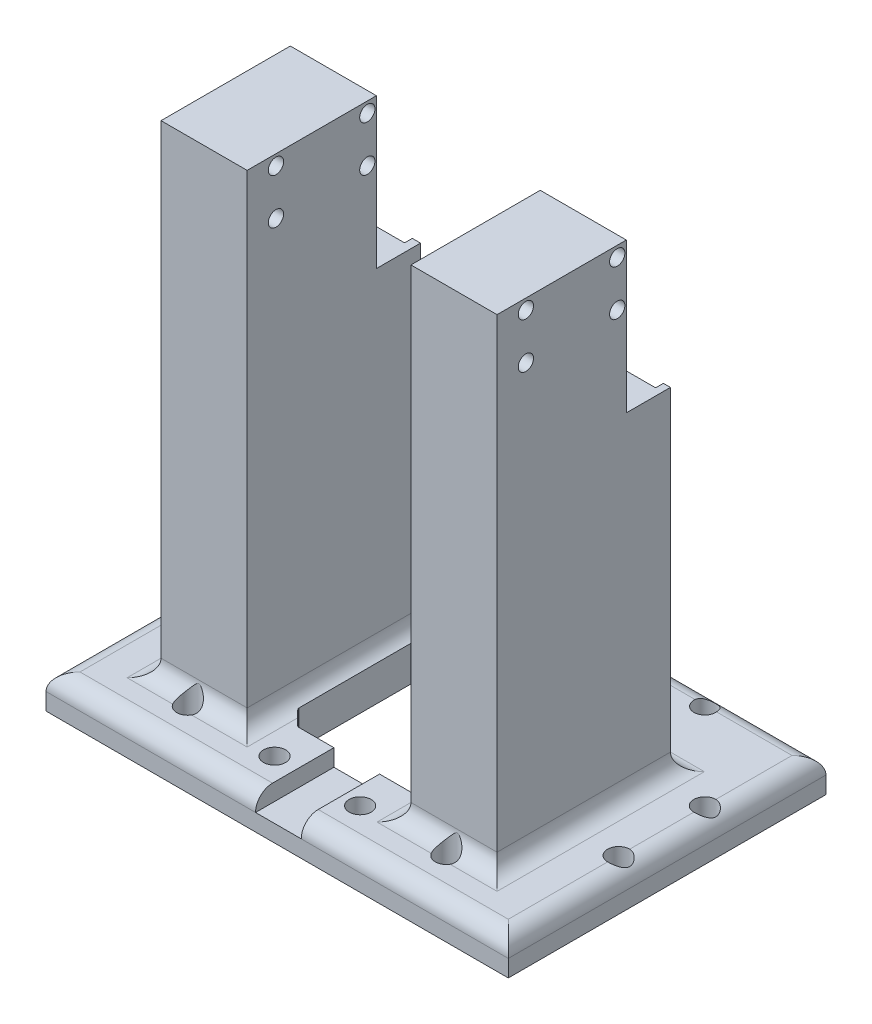
SolidWorks part; units mm, degrees
ref_plane "Front Plane" through (0, 0, 0) normal (0, 0, 1) x (1, 0, 0)
ref_plane "Top Plane" through (0, 0, 0) normal (0, 1, 0) x (1, 0, 0)
ref_plane "Right Plane" through (0, 0, 0) normal (1, 0, 0) x (0, 0, -1)
sketch "Sketch1" plane through (4645.495, -5615.4512, 222.287) normal (0, 1, 0) x (1, 0, 0)
  line L1 (-5.004, 249.919) -> (131.2605, 249.919)
  line L2 (-5.004, 249.919) -> (-5.004, 156.2902)
  line L4 (131.2605, 249.919) -> (131.2605, 156.2902)
  line L5 (-5.004, 156.2902) -> (63.1283, 156.2902)
  line L6 (63.1283, 156.2902) -> (131.2605, 156.2902)
extrude "Boss-Extrude1" add sketch "Sketch1" along normal blind 10
sketch "Sketch2" plane through (0, -5605.4512, 0) normal (0, 1, 0) x (1, 0, 0)
  line L0 (4708.449, 27.6321) -> (4708.449, -65.9968) construction
  line L1 (4658.9212, -50.5381) -> (4684.3037, -50.5381)
  line L2 (4658.9212, -50.5381) -> (4658.9212, 0.5715)
  line L3 (4658.9212, 0.5715) -> (4684.3037, 0.5715)
  line L4 (4684.3037, -50.5381) -> (4684.3037, 0.5715)
  line L6 (4640.4911, -65.9968) -> (4776.7555, -65.9968) construction
  line L7 (4732.5944, -50.5381) -> (4732.5944, 0.5715)
  line L8 (4757.9768, 0.5715) -> (4732.5944, 0.5715)
  line L9 (4757.9768, -50.5381) -> (4757.9768, 0.5715)
  line L10 (4757.9768, -50.5381) -> (4732.5944, -50.5381)
  line L11 (4640.4911, 27.6321) -> (4640.4911, -65.9968) construction
  dimension "D1" = 18.4301
  dimension "D2" = 43.8126
  dimension "D3" = 15.4587
  dimension "D4" = 66.5683
  dimension "D5" = 67.9579
extrude "Boss-Extrude2" add sketch "Sketch2" along normal blind 142.2321
sketch "Sketch3" plane through (0, 0, -0.5715) normal (0, 0, -1) x (-1, 0, 0)
  line L0 (-4737.0174, -5587.0652) -> (-4661.3426, -5587.0652) construction
  line L1 (-4661.3426, -5550.0756) -> (-4658.9212, -5550.0756) construction
  line L2 (-4661.3426, -5587.0652) -> (-4681.8823, -5587.0652)
  line L3 (-4661.3426, -5587.0652) -> (-4661.3426, -5463.2191)
  line L4 (-4661.3426, -5463.2191) -> (-4681.8823, -5463.2191)
  line L5 (-4681.8823, -5587.0652) -> (-4681.8823, -5463.2191)
  line L6 (-4658.9212, -5463.2191) -> (-4658.9212, -5605.4512) construction
  line L7 (-4681.8823, -5550.0756) -> (-4684.3037, -5550.0756) construction
  line L8 (-4684.3037, -5463.2191) -> (-4684.3037, -5605.4512) construction
  line L9 (-4684.3037, -5605.4512) -> (-4658.9212, -5605.4512) construction
  dimension "D1" = 2.4214
  dimension "D2" = 18.386
  dimension "D3" = 55.3755
  dimension "D4" = 142.2321
extrude "Cut-Extrude1" cut sketch "Sketch3" against normal blind 5.5
sketch "Sketch4" plane through (0, 0, 4.9285) normal (0, 0, -1) x (-1, 0, 0)
  line L0 (-4684.3037, -5463.2191) -> (-4684.3037, -5605.4512) construction
  line L1 (-4684.3037, -5507.3461) -> (-4658.9212, -5507.3461)
  line L2 (-4684.3037, -5507.3461) -> (-4684.3037, -5460.4819)
  line L3 (-4684.3037, -5460.4819) -> (-4658.9212, -5460.4819)
  line L4 (-4658.9212, -5507.3461) -> (-4658.9212, -5460.4819)
extrude "Cut-Extrude2" cut sketch "Sketch4" against normal blind 7.5 and the other way blind 12.5
fillet "Fillet14" radius 5 12 edges at (4745.2856, -5605.4512, -0.5715) (4732.5944, -5605.4512, 24.9833) (4745.2856, -5605.4512, 50.5381) (4757.9768, -5605.4512, 24.9833) (4684.3037, -5605.4512, 24.9833) (4671.6124, -5605.4512, -0.5715) (4658.9212, -5605.4512, 24.9833) (4671.6124, -5605.4512, 50.5381) (4708.6233, -5605.4512, -27.6321) (4776.7555, -5605.4512, 19.1824) (4708.6233, -5605.4512, 65.9968) (4640.4911, -5605.4512, 19.1824)
ref_plane "Plane1" through (4708.6233, 0, 0) normal (-1, 0, 0) x (0, 0, 1)
mirror "Mirror1" about plane through (4708.6233, 0, 0) normal (-1, 0, 0) of "Cut-Extrude1", "Cut-Extrude2"
sketch "Sketch5" plane through (0, 0, 4.9285) normal (0, 0, -1) x (-1, 0, 0)
  line L0 (-4661.3426, -5587.0652) -> (-4661.3426, -5507.3461) construction
  line L1 (-4661.3426, -5507.3461) -> (-4681.8823, -5507.3461) construction
  circle A0 centre (-4671.8428, -5574.7372) radius 1.6
  circle A1 centre (-4671.8428, -5528.736) radius 1.6
  circle A2 centre (-4745.0174, -5574.7372) radius 1.6
  circle A3 centre (-4745.0174, -5528.6285) radius 1.6
  dimension "D1" = 3.2
  dimension "D2" = 10.5002
  dimension "D3" = 83.6748
  dimension "D4" = 21.2824
  dimension "D5" = 21.3899
  dimension "D6" = 67.3911
extrude "Cut-Extrude3" cut sketch "Sketch5" against normal blind 5
sketch "Sketch6" plane through (0, -5615.4512, 0) normal (0, -1, 0) x (1, 0, 0)
  line L0 (4687.3481, 38.1501) -> (4687.3481, 5.4507)
  line L1 (4687.3481, 5.4507) -> (4687.3544, 5.3237)
  line L2 (4687.3544, 5.3237) -> (4687.3726, 5.2023)
  line L3 (4687.3726, 5.2023) -> (4687.4221, 5.0233)
  line L4 (4687.4221, 5.0233) -> (4687.4447, 4.9647)
  line L5 (4687.4447, 4.9647) -> (4687.5086, 4.8326)
  line L6 (4687.5086, 4.8326) -> (4687.5713, 4.7315)
  line L7 (4687.5713, 4.7315) -> (4687.6389, 4.6419)
  line L8 (4687.6389, 4.6419) -> (4687.72, 4.5526)
  line L9 (4687.72, 4.5526) -> (4687.845, 4.4277)
  line L10 (4687.845, 4.4277) -> (4691.1377, 1.135)
  line L11 (4691.1377, 1.135) -> (4691.2224, 1.0511)
  line L12 (4691.2224, 1.0511) -> (4691.2515, 1.0245)
  line L13 (4691.2515, 1.0245) -> (4691.2955, 0.9873)
  line L14 (4691.2955, 0.9873) -> (4691.3592, 0.9392)
  line L15 (4691.3592, 0.9392) -> (4691.4281, 0.8937)
  line L16 (4691.4281, 0.8937) -> (4691.5232, 0.8407)
  line L17 (4691.5232, 0.8407) -> (4691.6109, 0.7967)
  line L18 (4691.6109, 0.7967) -> (4691.844, 0.7303)
  line L19 (4691.844, 0.7303) -> (4691.8846, 0.7229)
  line L20 (4691.8846, 0.7229) -> (4692.0931, 0.7057)
  line L21 (4692.0931, 0.7057) -> (4724.7925, 0.7057)
  line L22 (4724.7925, 0.7057) -> (4724.9361, 0.7138)
  line L23 (4724.9361, 0.7138) -> (4725.0268, 0.7275)
  line L24 (4725.0268, 0.7275) -> (4725.101, 0.7437)
  line L25 (4725.101, 0.7437) -> (4725.1643, 0.7613)
  line L26 (4725.1643, 0.7613) -> (4725.2646, 0.7967)
  line L27 (4725.2646, 0.7967) -> (4725.3342, 0.827)
  line L28 (4725.3342, 0.827) -> (4725.3953, 0.8558)
  line L29 (4725.3953, 0.8558) -> (4725.4499, 0.8784)
  line L30 (4725.4499, 0.8784) -> (4725.4967, 0.9188)
  line L31 (4725.4967, 0.9188) -> (4725.5263, 0.9392)
  line L32 (4725.5263, 0.9392) -> (4729.1655, 4.5526)
  line L33 (4729.1655, 4.5526) -> (4729.2621, 4.661)
  line L34 (4729.2621, 4.661) -> (4729.2985, 4.7091)
  line L35 (4729.2985, 4.7091) -> (4729.3266, 4.7498)
  line L36 (4729.3266, 4.7498) -> (4729.347, 4.7816)
  line L37 (4729.347, 4.7816) -> (4729.3712, 4.8225)
  line L38 (4729.3712, 4.8225) -> (4729.3971, 4.8704)
  line L39 (4729.3971, 4.8704) -> (4729.4441, 4.9572)
  line L40 (4729.4441, 4.9572) -> (4729.4612, 5.0172)
  line L41 (4729.4612, 5.0172) -> (4729.4755, 5.0588)
  line L42 (4729.4755, 5.0588) -> (4729.496, 5.1286)
  line L43 (4729.496, 5.1286) -> (4729.5163, 5.1981)
  line L44 (4729.5163, 5.1981) -> (4729.5197, 5.2391)
  line L45 (4729.5197, 5.2391) -> (4729.5433, 5.4507)
  line L46 (4729.5433, 5.4507) -> (4729.5375, 38.0901)
  line L47 (4729.5375, 38.0901) -> (4729.5433, 38.1501)
  line L48 (4729.5433, 38.1501) -> (4729.5349, 38.2308)
  line L49 (4729.5349, 38.2308) -> (4729.5015, 38.4775)
  line L50 (4729.5015, 38.4775) -> (4729.3712, 38.7905)
  line L51 (4729.3712, 38.7905) -> (4729.2753, 38.9228)
  line L52 (4729.2753, 38.9228) -> (4729.1764, 39.0593)
  line L53 (4729.1764, 39.0593) -> (4725.6905, 42.5231)
  line L54 (4725.6905, 42.5231) -> (4725.5513, 42.6435)
  line L55 (4725.5513, 42.6435) -> (4725.4373, 42.7284)
  line L56 (4725.4373, 42.7284) -> (4725.1256, 42.8575)
  line L57 (4725.1256, 42.8575) -> (4724.7925, 42.9095)
  line L58 (4724.7925, 42.9095) -> (4692.1742, 42.8951)
  line L59 (4692.1742, 42.8951) -> (4691.7584, 42.8646)
  line L60 (4691.7584, 42.8646) -> (4691.4548, 42.7388)
  line L61 (4691.4548, 42.7388) -> (4691.1825, 42.5364)
  line L62 (4691.1825, 42.5364) -> (4687.72, 39.0481)
  line L63 (4687.72, 39.0481) -> (4687.4974, 38.7905)
  line L64 (4687.4974, 38.7905) -> (4687.3726, 38.4893)
  line L65 (4687.3726, 38.4893) -> (4687.3481, 38.1501)
  line L68 (4640.4911, -27.6321) -> (4640.4911, 65.9968) construction
  line L69 (4776.7555, -27.6321) -> (4640.4911, -27.6321) construction
  dimension "D1" = 46.857
  dimension "D2" = 46.8634
  dimension "D3" = 46.8815
  dimension "D4" = 46.9311
  dimension "D5" = 46.9537
  dimension "D6" = 47.0063
  dimension "D7" = 47.0175
  dimension "D8" = 47.0802
  dimension "D9" = 47.1478
  dimension "D10" = 47.229
  dimension "D11" = 47.3539
  dimension "D12" = 50.6466
  dimension "D13" = 50.6914
  dimension "D14" = 50.7313
  dimension "D15" = 50.7604
  dimension "D16" = 50.8045
  dimension "D17" = 50.8681
  dimension "D18" = 50.937
  dimension "D19" = 50.9637
  dimension "D20" = 51.0322
  dimension "D21" = 51.1198
  dimension "D22" = 51.2674
  dimension "D23" = 51.3529
  dimension "D24" = 51.3935
  dimension "D25" = 51.602
  dimension "D26" = 51.6831
  dimension "D27" = 84.3014
  dimension "D28" = 84.445
  dimension "D29" = 84.5357
  dimension "D30" = 84.61
  dimension "D31" = 84.6346
  dimension "D32" = 84.6733
  dimension "D33" = 84.7735
  dimension "D34" = 84.8432
  dimension "D35" = 84.9042
  dimension "D36" = 84.9462
  dimension "D37" = 84.9589
  dimension "D38" = 85.0056
  dimension "D39" = 85.0353
  dimension "D40" = 85.0602
  dimension "D41" = 85.1994
  dimension "D42" = 88.6744
  dimension "D43" = 88.6853
  dimension "D44" = 88.7711
  dimension "D45" = 88.7843
  dimension "D46" = 88.8074
  dimension "D47" = 88.8355
  dimension "D48" = 88.8559
  dimension "D49" = 88.8802
  dimension "D50" = 88.9061
  dimension "D51" = 88.953
  dimension "D52" = 88.9701
  dimension "D53" = 88.9844
  dimension "D54" = 89.0049
  dimension "D55" = 89.0104
  dimension "D56" = 89.0252
  dimension "D57" = 89.0287
  dimension "D58" = 89.0438
  dimension "D59" = 89.0464
  dimension "D60" = 89.0523
  dimension "D61" = 28.3377
  dimension "D62" = 28.3459
  dimension "D63" = 28.355
  dimension "D64" = 28.3595
  dimension "D65" = 28.3624
  dimension "D66" = 28.3758
  dimension "D67" = 28.3934
  dimension "D68" = 28.4287
  dimension "D69" = 28.4591
  dimension "D70" = 28.4727
  dimension "D71" = 28.4879
  dimension "D72" = 28.5105
  dimension "D73" = 28.5257
  dimension "D74" = 28.5509
  dimension "D75" = 28.5712
  dimension "D76" = 28.6194
  dimension "D77" = 28.6566
  dimension "D78" = 28.6831
  dimension "D79" = 28.7671
  dimension "D80" = 32.0598
  dimension "D81" = 32.4545
  dimension "D82" = 32.274
  dimension "D83" = 32.2931
  dimension "D84" = 32.3412
  dimension "D85" = 32.3635
  dimension "D86" = 32.3818
  dimension "D87" = 32.4137
  dimension "D88" = 32.5024
  dimension "D89" = 32.4647
  dimension "D90" = 32.6908
  dimension "D91" = 32.7607
  dimension "D92" = 32.5967
  dimension "D93" = 32.6492
  dimension "D94" = 32.6554
  dimension "D95" = 32.8343
  dimension "D96" = 33.0827
  dimension "D97" = 66.1214
  dimension "D98" = 66.4226
  dimension "D99" = 32.8712
  dimension "D100" = 32.9558
  dimension "D101" = 66.5549
  dimension "D102" = 65.7222
  dimension "D103" = 66.6802
  dimension "D104" = 65.8629
  dimension "D105" = 66.1095
  dimension "D106" = 70.1552
  dimension "D107" = 70.3605
  dimension "D112" = 70.1685
  dimension "D115" = 70.3709
  dimension "D117" = 70.4967
  dimension "D118" = 70.5271
  dimension "D119" = 70.5416
extrude "Cut-Extrude4" cut sketch "Sketch6" against normal through all
sketch "Sketch7" plane through (0, -5605.4512, 0) normal (0, 1, 0) x (1, 0, 0)
  line L0 (4692.1742, -42.8951) -> (4724.7925, -42.9095) construction
  line L1 (4702.2489, -42.8995) -> (4715.713, -42.8995)
  line L2 (4702.2489, -42.8995) -> (4702.2489, -65.9968)
  line L3 (4702.2489, -65.9968) -> (4715.713, -65.9968)
  line L4 (4715.713, -42.8995) -> (4715.713, -65.9968)
  line L5 (4776.7555, -65.9968) -> (4640.4911, -65.9968) construction
  line L6 (4653.9212, -55.5381) -> (4653.9212, 5.5715) construction
  dimension "D1" = 48.3277
  dimension "D2" = 61.7918
extrude "Cut-Extrude5" cut sketch "Sketch7" against normal blind 5
sketch "Sketch8" plane through (0, -5615.4512, 0) normal (0, -1, 0) x (1, 0, 0)
  line L0 (4687.3481, 38.1501) -> (4687.3481, 5.4507) construction
  circle A0 centre (4670.1499, 53.8638) radius 3.25
  circle A1 centre (4746.3499, 53.8638) radius 3.25
  circle A2 centre (4720.9499, 53.8638) radius 3.25
  circle A3 centre (4670.1499, -22.3362) radius 3.25
  circle A4 centre (4695.6719, 53.8142) radius 3.25
  circle A5 centre (4695.5499, -22.3362) radius 3.25
  circle A6 centre (4720.9499, -22.3362) radius 3.25
  circle A7 centre (4746.3499, -22.3362) radius 3.175
  circle A8 centre (4771.7499, 28.4638) radius 3.25
  circle A9 centre (4771.7499, 3.0638) radius 3.25
  circle A10 centre (4644.7499, 3.0638) radius 3.25
  circle A11 centre (4644.7499, 28.4638) radius 3.25
  dimension "D1" = 6.5
  dimension "D2" = 6.5
  dimension "D3" = 6.5
  dimension "D4" = 6.5
  dimension "D5" = 6.5
  dimension "D6" = 6.5
  dimension "D7" = 6.5
  dimension "D8" = 6.35
  dimension "D9" = 6.5
  dimension "D10" = 6.5
  dimension "D11" = 6.5
  dimension "D12" = 6.5
  dimension "D13" = 8.2019
  dimension "D14" = 8.3239
  dimension "D15" = 33.6019
  dimension "D16" = 59.0019
  dimension "D17" = 84.4019
  dimension "D18" = 17.1981
  dimension "D19" = 42.5981
  dimension "D20" = 15.3248
  dimension "D21" = 15.3744
  dimension "D22" = 10.0256
  dimension "D23" = 35.4256
  dimension "D24" = 60.8256
extrude "Cut-Extrude6" cut sketch "Sketch8" against normal through all
sketch "Sketch14" plane through (4658.9212, 0, 0) normal (-1, 0, 0) x (0, 0, 1)
  circle A0 centre (15.1109, -5466.3255) radius 2.25
  circle A1 centre (15.1109, -5479.7251) radius 2.25
  circle A2 centre (42.0393, -5479.7251) radius 2.25
  circle A3 centre (42.0393, -5466.3255) radius 2.25
  dimension "D1" = 4.5
extrude "Cut-Extrude7" cut sketch "Sketch14" against normal through all
sketch "Sketch18" plane through (0, 0, 12.4285) normal (0, 0, -1) x (-1, 0, 0)
  line L0 (-4732.5944, -5463.2191) -> (-4732.5944, -5600.4512) construction
  line L1 (-4757.9768, -5463.2191) -> (-4732.5944, -5463.2191)
  line L2 (-4757.9768, -5463.2191) -> (-4757.9768, -5507.3461)
  line L3 (-4757.9768, -5507.3461) -> (-4732.5944, -5507.3461)
  line L4 (-4732.5944, -5463.2191) -> (-4732.5944, -5507.3461)
  line L5 (-4757.9768, -5507.3461) -> (-4757.9768, -5463.2191) construction
  line L6 (-4732.9429, -5507.3461) -> (-4757.9768, -5507.3461) construction
extrude "Cut-Extrude10" cut sketch "Sketch18" along normal through all
sketch "Sketch19" plane through (0, 0, -0.5715) normal (0, 0, -1) x (-1, 0, 0)
  line L0 (-4684.3037, -5600.4512) -> (-4658.9212, -5600.4512) construction
  line L1 (-4681.8823, -5587.0652) -> (-4661.3426, -5587.0652)
  line L2 (-4681.8823, -5587.0652) -> (-4681.8823, -5600.4512)
  line L3 (-4681.8823, -5600.4512) -> (-4661.3426, -5600.4512)
  line L4 (-4661.3426, -5587.0652) -> (-4661.3426, -5600.4512)
  line L5 (-4661.3426, -5587.0652) -> (-4661.3426, -5507.3461) construction
extrude "Cut-Extrude11" cut sketch "Sketch19" against normal up to surface (5.5 mm away) up to face at (4670.2428, -5528.736, 4.9285)
sketch "Sketch20" plane through (0, 0, -0.5715) normal (0, 0, -1) x (-1, 0, 0)
  line L0 (-4757.9768, -5600.4512) -> (-4732.5944, -5600.4512) construction
  line L1 (-4755.904, -5587.0652) -> (-4735.3643, -5587.0652)
  line L2 (-4755.904, -5587.0652) -> (-4755.904, -5600.4512)
  line L3 (-4755.904, -5600.4512) -> (-4735.3643, -5600.4512)
  line L4 (-4735.3643, -5587.0652) -> (-4735.3643, -5600.4512)
  line L5 (-4735.3643, -5507.3461) -> (-4735.3643, -5587.0652) construction
extrude "Cut-Extrude12" cut sketch "Sketch20" against normal up to surface (5.5 mm away) up to face at (4743.4174, -5574.7372, 4.9285)
sketch "Sketch21" plane through (0, 0, 4.9285) normal (0, 0, -1) x (-1, 0, 0)
  line L0 (-4755.904, -5507.3461) -> (-4735.3643, -5507.3461) construction
  line L1 (-4755.904, -5507.3461) -> (-4735.3643, -5507.3461)
  line L2 (-4755.904, -5507.3461) -> (-4755.904, -5600.4512)
  line L3 (-4755.904, -5600.4512) -> (-4735.3643, -5600.4512)
  line L4 (-4735.3643, -5507.3461) -> (-4735.3643, -5600.4512)
  line L5 (-4681.8823, -5507.3461) -> (-4661.3426, -5507.3461)
  line L6 (-4681.8823, -5507.3461) -> (-4681.8823, -5600.4512)
  line L7 (-4681.8823, -5600.4512) -> (-4661.3426, -5600.4512)
  line L8 (-4661.3426, -5507.3461) -> (-4661.3426, -5600.4512)
  circle A0 centre (-4745.0174, -5574.7372) radius 1.6
  circle A1 centre (-4745.0174, -5528.6285) radius 1.6
  circle A2 centre (-4671.8428, -5574.7372) radius 1.6
  circle A3 centre (-4671.8428, -5528.736) radius 1.6
  dimension "D1" = 3.2
extrude "Boss-Extrude3" add sketch "Sketch21" along normal blind 3.2069
